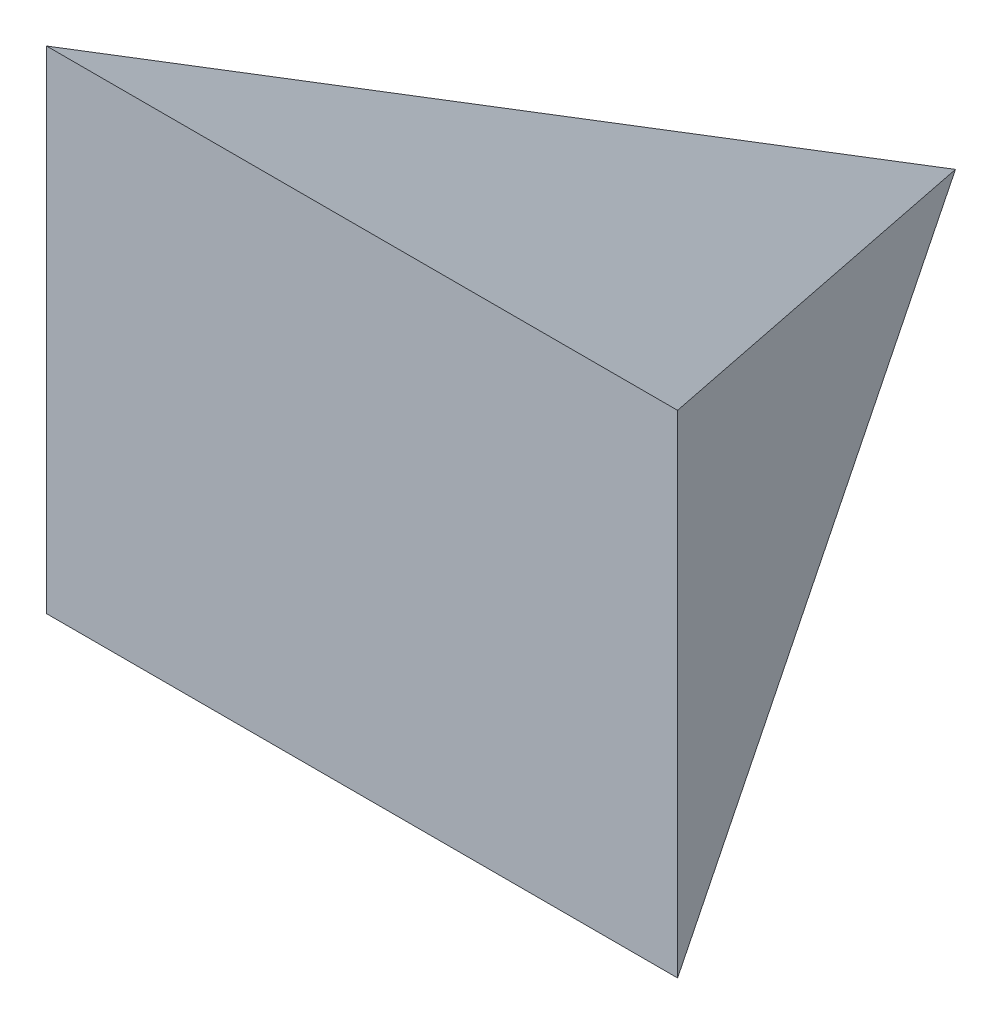
SolidWorks part; units mm, degrees
ref_plane "Front Plane" through (0, 0, 0) normal (0, 0, 1) x (1, 0, 0)
ref_plane "Top Plane" through (0, 0, 0) normal (0, 1, 0) x (1, 0, 0)
ref_plane "Right Plane" through (0, 0, 0) normal (1, 0, 0) x (0, 0, -1)
sketch "Sketch1" plane through (0, 0, 0) normal (0, 1, 0) x (1, 0, 0)
  line L0 (0, 0) -> (-106.3419, -200)
  line L1 (-106.3419, -200) -> (106.3419, -200)
  line L2 (106.3419, -200) -> (0, 0)
  dimension "D1" = 200
  dimension "D2" = 56
extrude "Boss-Extrude1" add sketch "Sketch1" along normal blind 200
sketch "Sketch2" plane through (0, 0, 0) normal (1, 0, 0) x (0, 0, -1)
  line L0 (0, 100) -> (-200, 182.8427)
  line L1 (0, 200) -> (0, 0) construction
  line L2 (-200, 200) -> (-200, 0) construction
  line L3 (-200, 182.8427) -> (-200, 17.1573)
  line L4 (-200, 17.1573) -> (0, 100)
  dimension "D1" = 45
extrude "Cut-Extrude1" cut sketch "Sketch2" against normal through all and the other way through all flip side to cut
